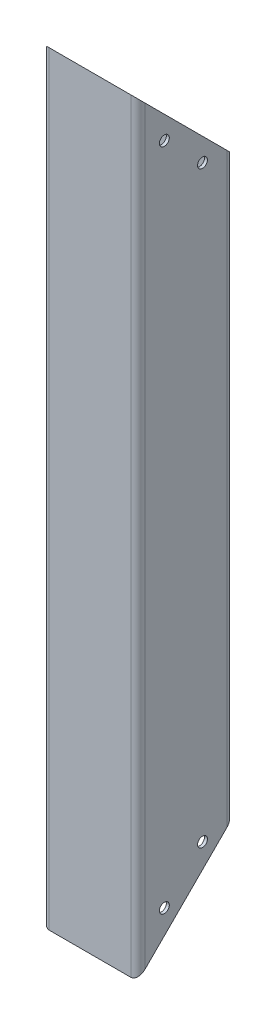
SolidWorks part; units mm, degrees
note: '?' marks a value the reader was unsure of.
material "Carbon Fiber, Plain Weave"
ref_plane "Front Plane" through (0, 0, 0) normal (0, 0, 1) x (1, 0, 0)
ref_plane "Top Plane" through (0, 0, 0) normal (0, 1, 0) x (1, 0, 0)
ref_plane "Right Plane" through (0, 0, 0) normal (1, 0, 0) x (0, 0, -1)
ref_axis "Axis1" through (0, 0, -88.99) along (0, 0, 1)?
ref_axis "Axis2" through (0, -55, 0) along (0, 1, 0)?
ref_axis "Axis3" through (-88.99, 0, 0) along (1, 0, 0)?
sketch "Sketch1" plane through (0, 0, 0) normal (1, 0, 0) x (0, 0, -1)
  line L0 (0, 0) -> (0, 425)
  dimension "D1" = 425
other "Structural Member1" corner treatment miter
ref_plane "Plane1" through (0, 0, 0) normal (0, 1, 0) x (0, 0, 1)
sketch "Sketch16" plane through (0, 0, 0) normal (0, 1, 0) x (0, 0, 1)
  line L0 (-26.67, 22.7012) -> (-26.67, -22.7013)
  line L1 (-22.7012, -26.67) -> (22.7012, -26.67)
  line L2 (-22.7013, 26.67) -> (22.7012, 26.67)
  line L3 (26.67, 22.7012) -> (26.67, -22.7013)
  line L4 (-26.67, 26.67) -> (26.67, -26.67) construction
  line L5 (-25.019, 22.7012) -> (-25.019, -22.7013)
  line L6 (-22.7012, -25.019) -> (22.7012, -25.019)
  line L7 (25.019, 22.7012) -> (25.019, -22.7013)
  line L8 (-22.7013, 25.019) -> (22.7012, 25.019)
  arc A0 (-26.67, -22.7013) -> (-22.7012, -26.67) centre (-22.7012, -22.7013) ccw
  arc A1 (22.7012, -26.67) -> (26.67, -22.7013) centre (22.7012, -22.7013) ccw
  arc A2 (22.7012, 26.67) -> (26.67, 22.7012) centre (22.7012, 22.7012) cw
  arc A3 (-26.67, 22.7012) -> (-22.7013, 26.67) centre (-22.7013, 22.7012) cw
  arc A4 (-25.019, -22.7013) -> (-22.7012, -25.019) centre (-22.7012, -22.7013) ccw
  arc A5 (22.7012, -25.019) -> (25.019, -22.7013) centre (22.7012, -22.7013) ccw
  arc A6 (22.7012, 25.019) -> (25.019, 22.7012) centre (22.7012, 22.7012) cw
  arc A7 (-25.019, 22.7012) -> (-22.7013, 25.019) centre (-22.7013, 22.7012) cw
  point P6 (-26.67, -26.67)
  point P28 (0, 0)
  dimension "CORNER_RADIUS" = 3.9688
  dimension "THICKNESS" = 1.651
  dimension "VERT LEG" = 53.34
  dimension "HORZ LEG" = 53.34
sketch "Sketch12" plane through (26.67, 0, 0) normal (1, 0, 0) x (0, 0, -1)
  line L0 (-26.67, 425) -> (26.67, 371.66)
  line L2 (26.67, 371.66) -> (26.67, 425)
  line L3 (26.67, 425) -> (-26.67, 425)
  line L4 (-22.7012, 212.5) -> (22.7013, 212.5) construction
  line L6 (26.67, 0) -> (-26.67, 0)
  line L7 (26.67, 53.34) -> (26.67, 0)
  line L8 (-26.67, 0) -> (26.67, 53.34)
  line L9 (26.67, 425) -> (26.67, 0) construction
  line L10 (-22.7012, 425) -> (-22.7012, 0) construction
  line L11 (22.7013, 425) -> (22.7013, 0) construction
  dimension "D1" = 45
extrude "Cut-Extrude1" cut sketch "Sketch12" against normal through all
hole_wizard "M5 Clearance Hole1" positions "Sketch14" profile "Sketch13" hole size "M5" standard "ANSI Metric" end condition through all
sketch "Sketch14" plane through (26.67, 0, 0) normal (1, 0, 0) x (0, 0, -1)
  line L0 (-12.0208, 397.6229) -> (9.1924, 376.4097) construction
  line L2 (0, 385.6021) -> (0, 0) construction
  line L4 (-12.0208, 28.0842) -> (9.1924, 49.2974) construction
  line L6 (22.7013, 49.3713) -> (-22.7012, 3.9688) construction
  line L7 (-22.7013, 421.0312) -> (22.7013, 375.6287) construction
  line L8 (-1.4142, 38.6908) -> (5.3033, 31.9733) construction
  line L10 (0, 40.105) -> (6.7175, 33.3875) construction
  line L11 (-1.4142, 387.0163) -> (4.9497, 393.3803) construction
  line L13 (0, 385.6021) -> (6.364, 391.966) construction
  point P0 (-12.0208, 397.6229)
  point P2 (9.1924, 376.4097)
  point P4 (-12.0208, 28.0842)
  point P6 (9.1924, 49.2974)
  dimension "D1" = 30
  dimension "D2" = 9.5
  dimension "D3" = 9
  dimension "D4" = 30
  dimension "D5" = 2
  dimension "D6" = 2
sketch "Sketch13" plane through (26.67, 397.6229, 12.0208) normal (0, 1, 0) x (0, 0, -1)
  line L0 (0, 0) -> (0, 53.34)
  line L1 (0, 53.34) -> (2.75, 53.34)
  line L2 (2.75, 53.34) -> (2.75, 0)
  line L5 (2.75, 0) -> (0, 0)
  line L11 (0, -6.35) -> (0, 107.95) construction
  dimension "Thru Hole Dia." = 5.5
  dimension "Thru Hole Depth" = 53.34
